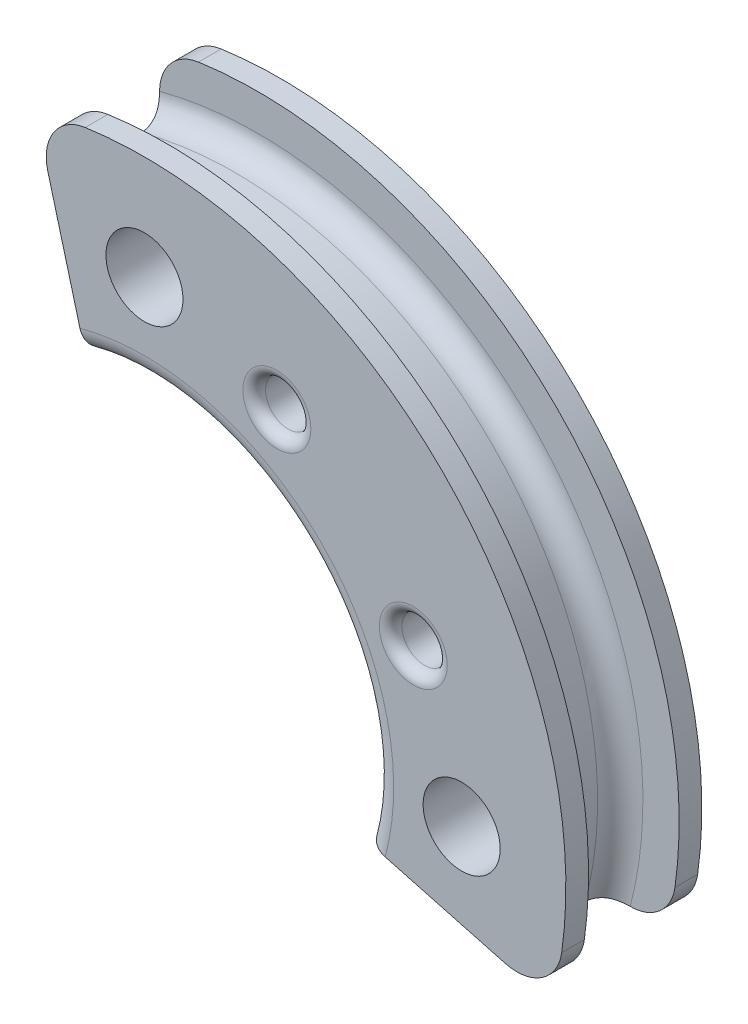
SolidWorks part; units mm, degrees
ref_plane "Front" through (0, 0, 0) normal (0, 0, 1) x (1, 0, 0)
ref_plane "Top" through (0, 0, 0) normal (0, 1, 0) x (1, 0, 0)
ref_plane "Right" through (0, 0, 0) normal (1, 0, 0) x (0, 0, -1)
sketch "Sketch1" plane through (0, 0, 0) normal (0, 0, 1) x (1, 0, 0)
  line L0 (0, 7) -> (0, -7) construction
  circle A2 centre (7, 0) radius 0.85
  circle A24 centre (0, 0) radius 8.5
  circle A25 centre (0, 0) radius 5
  circle A30 centre (0, -7) radius 0.85
  circle A32 centre (-7, 0) radius 0.85
  circle A34 centre (0, 7) radius 0.85
  point P20 (0, 0)
  dimension "D1" = 4
  dimension "D2" = 17
  dimension "D3" = 10
  dimension "D5" = 1.7
  dimension "D4" = 14
extrude "Boss-Extrude1" add sketch "Sketch1" along normal mid plane 3
sketch "Sketch2" plane through (0, 0, 0) normal (0, 1, 0) x (1, 0, 0)
  line L1 (0, 0) -> (0, 3.24) construction
  line L2 (-8, 0.5) -> (-8, -0.5)
  line L3 (-8, 0) -> (-8.5, 0) construction
  line L4 (-8.5, 1.5) -> (-8.5, -1.5) construction
  line L5 (-8.5, -1) -> (-8.5, 1)
  arc A1 (-8.5, 1) -> (-8, 0.5) centre (-8.5, 0.5) cw
  arc A2 (-8.5, -1) -> (-8, -0.5) centre (-8.5, -0.5) ccw
  dimension "D1" = 2
  dimension "D2" = 16
revolve "Cut-Revolve1" cut sketch "Sketch2" angle 360 about L1
sketch "Sketch7" plane through (0, 0, 0) normal (0, 1, 0) x (1, 0, 0)
  line L0 (0, 0) -> (11.0142, 0) construction
  line L1 (8.5, 1.5) -> (9.3, 1.5)
  line L2 (8.5, 1.5) -> (8.5, 1)
  line L3 (8.5, 1) -> (9.3, 1)
  line L4 (9.3, 1.5) -> (9.3, 1)
  line L5 (9.3, -1.5) -> (9.3, -1)
  line L6 (8.5, -1) -> (9.3, -1)
  line L7 (8.5, -1.5) -> (8.5, -1)
  line L8 (8.5, -1.5) -> (9.3, -1.5)
  line L9 (8.5, 1) -> (-8.5, 1) construction
  line L10 (0, 0) -> (0, 2.6862) construction
  dimension "D1" = 0.8
revolve "Revolve1" add sketch "Sketch7" angle 360 about L10
sketch "Sketch4" plane through (0, 0, 0) normal (0, 0, 1) x (1, 0, 0)
  line L0 (-2.6543, 9.9058) -> (0, 0)
  line L1 (0, 0) -> (6.0104, 6.0104) construction
  line L2 (0, 0) -> (-16.6927, 0) construction
  line L3 (10.3501, -2.7733) -> (0, 0)
  line L5 (-2.6543, 9.9058) -> (-11.3342, 9.9058)
  line L6 (-11.3342, 9.9058) -> (-11.3342, -11.0336)
  line L7 (-11.3342, -11.0336) -> (10.3501, -11.0336)
  line L10 (10.3501, -2.7733) -> (10.3501, -11.0336)
  dimension "D3" = 60
  dimension "D1" = 135
  dimension "D2" = 120
extrude "Cut-Extrude1" cut sketch "Sketch4" against normal through all both and the other way through all
sketch "Sketch5" plane through (0, 0, 1.5) normal (0, 0, 1) x (1, 0, 0)
  line L1 (0, 0) -> (6.5761, 6.5761) construction
  circle A1 centre (2.9224, 5.9323) radius 0.5
  arc A2 (8.9831, -2.407) -> (-2.407, 8.9831) centre (0, 0) ccw construction
  circle A3 centre (5.9323, 2.9224) radius 0.5
  point P9 (2.6856, 5.6323)
  point P11 (2.9224, 5.9323)
  dimension "D1" = 1
extrude "Cut-Extrude2" cut sketch "Sketch5" against normal through all both and the other way through all
fillet "Fillet1" radius 0.5 2 edges at (3.5355, 3.5355, 1.5) (3.5355, 3.5355, -1.5)
sketch "Sketch6" plane through (0, 0, 0) normal (0, 0, 1) x (1, 0, 0)
  circle A0 centre (0, 0) radius 8
  dimension "D1" = 16
fillet "Fillet2" radius 1 4 edges at (8.9831, -2.407, -1.25) (8.9831, -2.407, 1.25) (-2.407, 8.9831, -1.25) (-2.407, 8.9831, 1.25)
chamfer "Chamfer1" distance 0.8 angle 45 2 edges at (7.85, 0, -1.5) (0.85, 7, -1.5)
fillet "Fillet3" radius 0.25 4 edges at (5.4323, 2.9224, -1.5) (6.4323, 2.9224, 1.5) (3.4224, 5.9323, -1.5) (3.4224, 5.9323, 1.5)
